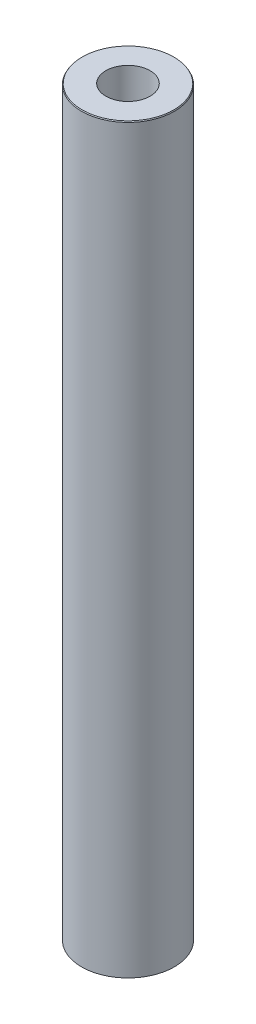
SolidWorks part; units mm, degrees
ref_plane "Front Plane" through (0, 0, 0) normal (0, 0, 1) x (1, 0, 0)
ref_plane "Top Plane" through (0, 0, 0) normal (0, 1, 0) x (1, 0, 0)
ref_plane "Right Plane" through (0, 0, 0) normal (1, 0, 0) x (0, 0, -1)
sketch "Sketch1" plane through (0, 0, 0) normal (0, 1, 0) x (1, 0, 0)
  circle A0 centre (0, 0) radius 37.5
  dimension "SHAFT_OD" = 75
extrude "Boss-Extrude1" add sketch "Sketch1" along normal blind 600
sketch "Sketch2" plane through (0, 0, 0) normal (0, 1, 0) x (1, 0, 0)
  circle A0 centre (0, 0) radius 17.8987
  dimension "BORE_D" = 35.7973
extrude "Cut-Extrude1" cut sketch "Sketch2" along normal through all
chamfer "Chamfer1" distance 0.794 angle 30 2 edges at (0, 600, 37.5) (0, 0, 37.5) first distance on face at (0, 600, 37.5) first distance on face at (0, 0, 17.8987)
